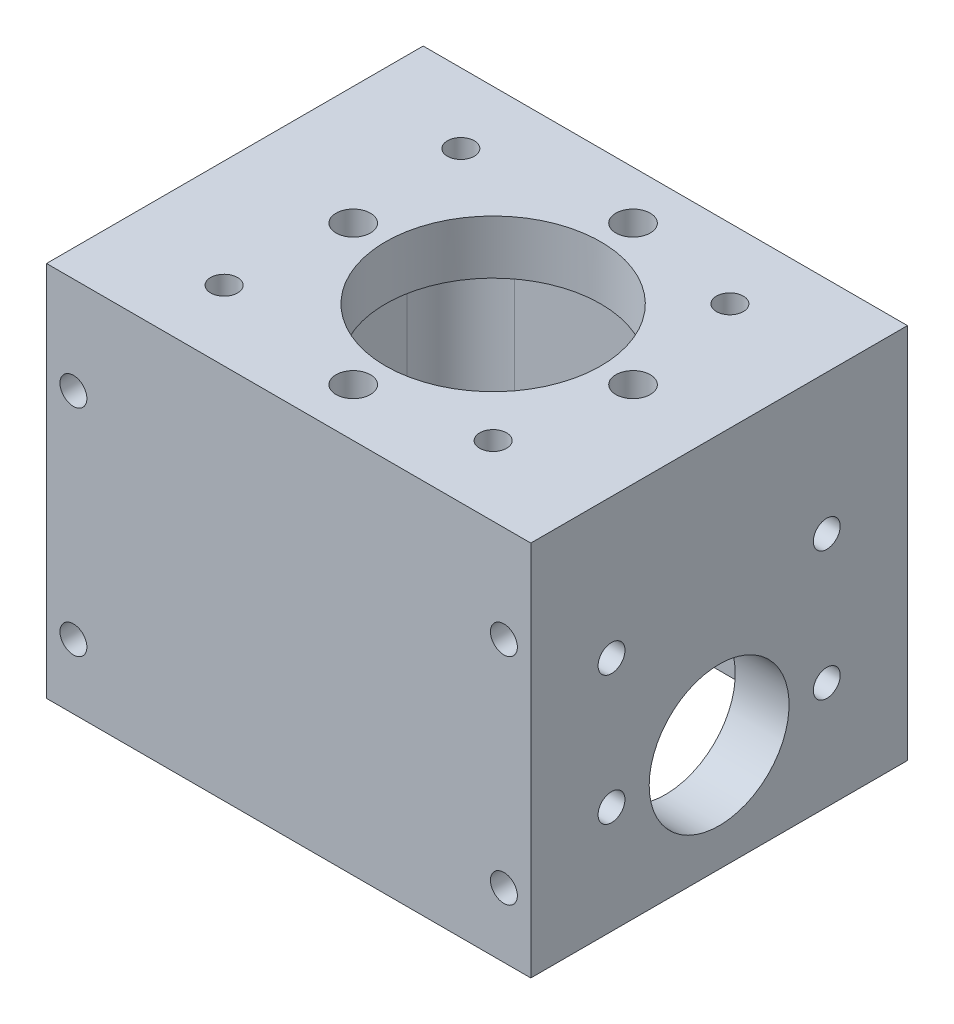
SolidWorks part; units mm, degrees
ref_plane "Plan de face" through (0, 0, 0) normal (0, 0, 1) x (1, 0, 0)
ref_plane "Plan de dessus" through (0, 0, 0) normal (0, 1, 0) x (1, 0, 0)
ref_plane "Plan de droite" through (0, 0, 0) normal (1, 0, 0) x (0, 0, -1)
sketch "Esquisse1" plane through (0, 0, 0) normal (0, 0, 1) x (1, 0, 0)
  line L1 (-22.5, 17.5) -> (22.5, 17.5)
  line L2 (-22.5, 17.5) -> (-22.5, -17.5)
  line L3 (-22.5, -17.5) -> (22.5, -17.5)
  line L4 (22.5, 17.5) -> (22.5, -17.5)
  line L5 (-22.5, 17.5) -> (22.5, -17.5) construction
  line L6 (-22.5, -17.5) -> (22.5, 17.5) construction
  point P0 (0, 0)
  dimension "D1" = 45
  dimension "D2" = 35
extrude "Boss.-Extru.1" add sketch "Esquisse1" along normal blind 35
sketch "Esquisse2" plane through (0, 17.5, 0) normal (0, 1, 0) x (1, 0, 0)
  line L0 (-22.5, -17.5) -> (1.5, -17.5) construction
  line L1 (-22.5, -35) -> (-22.5, 0) construction
  line L2 (22.5, -35) -> (22.5, 0) construction
  circle A0 centre (1.5, -17.5) radius 10
  dimension "D1" = 20
  dimension "D2" = 21
extrude "Enlèv. mat.-Extru.1" cut sketch "Esquisse2" against normal blind 10
sketch "Esquisse3" plane through (0, -17.5, 0) normal (0, -1, 0) x (1, 0, 0)
  line L0 (-22.5, 35) -> (22.5, 35) construction
  line L1 (17.5, 0) -> (-17.5, 0)
  line L2 (17.5, 0) -> (17.5, 35)
  line L3 (17.5, 35) -> (-17.5, 35)
  line L4 (-17.5, 0) -> (-17.5, 35)
  line L5 (17.5, 0) -> (-17.5, 35) construction
  line L6 (17.5, 35) -> (-17.5, 0) construction
  line L7 (-22.5, 35) -> (-22.5, 0) construction
  point P0 (0, 17.5)
  point P9 (0, 0)
  dimension "D1" = 5
extrude "Enlèv. mat.-Extru.2" cut sketch "Esquisse3" against normal offset from surface (30 mm away) 5 up to face at (1.5, 17.5, 27.5)
sketch "Esquisse4" plane through (-22.5, 0, 0) normal (-1, 0, 0) x (0, 0, 1)
  line L0 (17.5, -17.5) -> (17.5, -7.5) construction
  line L1 (35, -17.5) -> (0, -17.5) construction
  circle A0 centre (17.5, -7.5) radius 6.5
  dimension "D1" = 13
  dimension "D2" = 10
extrude "Enlèv. mat.-Extru.3" cut sketch "Esquisse4" against normal through all
sketch "Esquisse15" plane through (0, 12.5, 0) normal (0, -1, 0) x (1, 0, 0)
  line L0 (17.5, 35) -> (17.5, 0) construction
  line L1 (-17.5, 35) -> (17.5, 35)
  line L2 (-17.5, 35) -> (-17.5, 33.5)
  line L3 (-17.5, 33.5) -> (17.5, 33.5)
  line L4 (17.5, 35) -> (17.5, 33.5)
  line L6 (-17.5, 0) -> (17.5, 0)
  line L7 (-17.5, 0) -> (-17.5, 1.5)
  line L8 (-17.5, 1.5) -> (17.5, 1.5)
  line L9 (17.5, 0) -> (17.5, 1.5)
  dimension "D1" = 1.5
extrude "Boss.-Extru.2" add sketch "Esquisse15" along normal up to surface (30 mm away) up to face at (-20, -17.5, 17.5)
fillet "Congé1" radius 5 4 edges at (17.5, -2.5, 33.5) (-17.5, -2.5, 1.5) (17.5, -2.5, 1.5) (-17.5, -2.5, 33.5)
hole_wizard "Diamètre du perçage Ø3.2 (3.2)1" positions "Esquisse6" profile "Esquisse5" hole size "Ø3.2" standard "ISO"
sketch "Esquisse6" plane through (0, 12.5, 0) normal (0, -1, 0) x (-1, 0, 0)
  circle A0 centre (-1.5, -17.5) radius 13
  point P4 (-14.5, -17.5)
  point P6 (-1.5, -4.5)
  point P8 (11.5, -17.5)
  point P10 (-1.5, -30.5)
  dimension "D1" = 26
sketch "Esquisse5" plane through (14.5, 12.5, 17.5) normal (1, 0, 0) x (0, 0, -1)
  line L0 (0, 0) -> (0, 7)
  line L1 (0, 7) -> (1.6, 7)
  line L2 (1.6, 7) -> (1.6, 0)
  line L5 (1.6, 0) -> (0, 0)
  line L10 (0, 7) -> (-1.6, 7) construction
  line L11 (0, -6.35) -> (0, 107.95) construction
  dimension "Diamètre du perçage" = 3.2
  dimension "Profondeur du perçage" = 7
  dimension "Angle de pointe" = 180
hole_wizard "Trou taraudé M3x0.52" positions "Esquisse8" profile "Esquisse7" tap size "M3x0.5" standard "Ansi Metric"
sketch "Esquisse8" plane through (0, -17.5, 0) normal (0, -1, 0) x (-1, 0, 0)
  line L1 (-20, -7.5) -> (20, -7.5)
  line L2 (-20, -7.5) -> (-20, -27.5)
  line L3 (-20, -27.5) -> (20, -27.5)
  line L4 (20, -7.5) -> (20, -27.5)
  line L5 (-22.5, -17.5) -> (-20, -17.5)
  line L6 (-22.5, -35) -> (-22.5, 0) construction
  line L8 (0, -7.5) -> (0, 0)
  line L10 (20, -17.5) -> (22.5, -17.5)
  line L11 (22.5, -35) -> (22.5, 0) construction
  line L13 (0, -27.5) -> (0, -35)
  line L14 (17.5, -35) -> (-17.5, -35) construction
  point P1 (-20, -7.5)
  point P2 (20, -27.5)
  point P105 (-20, -27.5)
  point P106 (20, -7.5)
  dimension "D1" = 40
  dimension "D2" = 20
sketch "Esquisse7" plane through (20, -17.5, 7.5) normal (1, 0, 0) x (0, 0, -1)
  line L0 (0, 0) -> (0, 7.2511)
  line L1 (0, 7.2511) -> (1.25, 6.5)
  line L2 (1.25, 6.5) -> (1.25, 0)
  line L5 (1.25, 0) -> (0, 0)
  line L10 (0, 7.2511) -> (-1.25, 6.5) construction
  line L11 (0, -6.35) -> (0, 107.95) construction
  dimension "Diamètre du trou pour taraudage" = 2.5
  dimension "Profondeur du trou pour taraudage" = 6.5
  dimension "Angle de pointe" = 118
cosmetic thread "Filetage de perçage1" parameters "D1"=4, "D2"=3
cosmetic thread "Filetage de perçage2" parameters "D1"=4, "D2"=3
cosmetic thread "Filetage de perçage3" parameters "D1"=4, "D2"=3
cosmetic thread "Filetage de perçage4" parameters "D1"=4, "D2"=3
hole_wizard "Trou taraudé M3x0.53" positions "Esquisse10" profile "Esquisse9" tap size "M3x0.5" standard "Ansi Metric"
sketch "Esquisse10" plane through (0, 0, 0) normal (0, 0, -1) x (-1, 0, 0)
  line L1 (-20, 8.5) -> (20, 8.5)
  line L2 (-20, 8.5) -> (-20, -11.5)
  line L3 (-20, -11.5) -> (20, -11.5)
  line L4 (20, 8.5) -> (20, -11.5)
  line L5 (-22.5, -17.5) -> (-22.5, 17.5) construction
  line L6 (22.5, -17.5) -> (-22.5, -17.5) construction
  point P1 (-20, 8.5)
  point P2 (20, -11.5)
  point P149 (-20, -11.5)
  point P150 (20, 8.5)
  dimension "D1" = 40
  dimension "D2" = 20
  dimension "D3" = 2.5
  dimension "D4" = 6
sketch "Esquisse9" plane through (20, 8.5, 0) normal (1, 0, 0) x (0, 1, 0)
  line L0 (0, 0) -> (0, 7.2511)
  line L1 (0, 7.2511) -> (1.25, 6.5)
  line L2 (1.25, 6.5) -> (1.25, 0)
  line L5 (1.25, 0) -> (0, 0)
  line L10 (0, 7.2511) -> (-1.25, 6.5) construction
  line L11 (0, -6.35) -> (0, 107.95) construction
  dimension "Diamètre du trou pour taraudage" = 2.5
  dimension "Profondeur du trou pour taraudage" = 6.5
  dimension "Angle de pointe" = 118
cosmetic thread "Filetage de perçage5" parameters "D1"=4, "D2"=3
cosmetic thread "Filetage de perçage6" parameters "D1"=4, "D2"=3
cosmetic thread "Filetage de perçage7" parameters "D1"=4, "D2"=3
cosmetic thread "Filetage de perçage8" parameters "D1"=4, "D2"=3
hole_wizard "Trou taraudé M3x0.54" positions "Esquisse12" profile "Esquisse11" tap size "M3x0.5" standard "Ansi Metric"
sketch "Esquisse12" plane through (0, 0, 35) normal (0, 0, 1) x (1, 0, 0)
  line L24 (20, 8.5) -> (-20, 8.5)
  line L25 (20, -11.5) -> (20, 8.5)
  line L26 (-20, -11.5) -> (20, -11.5)
  line L27 (-20, 8.5) -> (-20, -11.5)
  line L28 (20, 8.5) -> (-20, 8.5)
  line L29 (20, -11.5) -> (20, 8.5)
  line L30 (-20, -11.5) -> (20, -11.5)
  line L31 (-20, 8.5) -> (-20, -11.5)
  point P75 (20, 8.5)
  point P76 (-20, 8.5)
  point P78 (20, -11.5)
  point P80 (-20, -11.5)
  dimension "D1" = 0
sketch "Esquisse11" plane through (20, 8.5, 35) normal (1, 0, 0) x (0, -1, 0)
  line L0 (0, 0) -> (0, 7.2511)
  line L1 (0, 7.2511) -> (1.25, 6.5)
  line L2 (1.25, 6.5) -> (1.25, 0)
  line L5 (1.25, 0) -> (0, 0)
  line L10 (0, 7.2511) -> (-1.25, 6.5) construction
  line L11 (0, -6.35) -> (0, 107.95) construction
  dimension "Diamètre du trou pour taraudage" = 2.5
  dimension "Profondeur du trou pour taraudage" = 6.5
  dimension "Angle de pointe" = 118
cosmetic thread "Filetage de perçage9" parameters "D1"=4, "D2"=3
cosmetic thread "Filetage de perçage10" parameters "D1"=4, "D2"=3
cosmetic thread "Filetage de perçage11" parameters "D1"=4, "D2"=3
cosmetic thread "Filetage de perçage12" parameters "D1"=4, "D2"=3
hole_wizard "Trou taraudé M3x0.56" positions "Esquisse14" profile "Esquisse13" tap size "M3x0.5" standard "Ansi Metric"
sketch "Esquisse14" plane through (22.5, 0, 0) normal (1, 0, 0) x (0, 0, -1)
  line L1 (-27.5, -7.5) -> (-7.5, -7.5)
  line L2 (-27.5, -7.5) -> (-27.5, 4.5)
  line L3 (-27.5, 4.5) -> (-7.5, 4.5)
  line L4 (-7.5, -7.5) -> (-7.5, 4.5)
  line L5 (-17.5, -17.5) -> (-17.5, -7.5)
  line L6 (-35, -17.5) -> (0, -17.5) construction
  point P1 (-27.5, -7.5)
  point P2 (-7.5, 4.5)
  point P113 (-27.5, 4.5)
  point P114 (-7.5, -7.5)
  dimension "D1" = 12
  dimension "D2" = 20
  dimension "D3" = 10
sketch "Esquisse13" plane through (22.5, -7.5, 27.5) normal (0, 1, 0) x (0, 0, -1)
  line L0 (0, 0) -> (0, 7.2511)
  line L1 (0, 7.2511) -> (1.25, 6.5)
  line L2 (1.25, 6.5) -> (1.25, 0)
  line L5 (1.25, 0) -> (0, 0)
  line L10 (0, 7.2511) -> (-1.25, 6.5) construction
  line L11 (0, -6.35) -> (0, 107.95) construction
  dimension "Diamètre du trou pour taraudage" = 2.5
  dimension "Profondeur du trou pour taraudage" = 6.5
  dimension "Angle de pointe" = 118
cosmetic thread "Filetage de perçage13" parameters "D1"=4, "D2"=3
cosmetic thread "Filetage de perçage14" parameters "D1"=4, "D2"=3
cosmetic thread "Filetage de perçage15" parameters "D1"=4, "D2"=3
cosmetic thread "Filetage de perçage16" parameters "D1"=4, "D2"=3
hole_wizard "Trou taraudé M3x0.57" positions "Esquisse17" profile "Esquisse16" tap size "M3x0.5" standard "Ansi Metric" end condition through all
sketch "Esquisse17" plane through (0, 12.5, 0) normal (0, -1, 0) x (-1, 0, 0)
  line L1 (-12.5, -28.5) -> (12.5, -28.5)
  line L2 (-12.5, -28.5) -> (-12.5, -6.5)
  line L3 (-12.5, -6.5) -> (12.5, -6.5)
  line L4 (12.5, -28.5) -> (12.5, -6.5)
  line L5 (-17.5, -17.5) -> (-12.5, -17.5)
  line L6 (-17.5, -28.5) -> (-17.5, -6.5) construction
  line L8 (0, -6.5) -> (0, -1.5)
  line L9 (-12.5, -1.5) -> (12.5, -1.5) construction
  point P0 (-12.5, -28.5)
  point P1 (12.5, -6.5)
  point P6 (-12.5, -6.5)
  point P7 (12.5, -28.5)
  dimension "D1" = 25
  dimension "D2" = 22
sketch "Esquisse16" plane through (12.5, 12.5, 28.5) normal (1, 0, 0) x (0, 0, -1)
  line L0 (0, 0) -> (0, 5)
  line L1 (0, 5) -> (1.25, 5)
  line L2 (1.25, 5) -> (1.25, 0)
  line L5 (1.25, 0) -> (0, 0)
  line L11 (0, -6.35) -> (0, 107.95) construction
  dimension "Diamètre du trou pour taraudage jusqu'au prochain" = 2.5
  dimension "Profondeur du trou pour taraudage jusqu'au prochain" = 5
cosmetic thread "Filetage de perçage17" parameters "D2"=3
cosmetic thread "Filetage de perçage18" parameters "D2"=3
cosmetic thread "Filetage de perçage19" parameters "D2"=3
cosmetic thread "Filetage de perçage20" parameters "D2"=3
